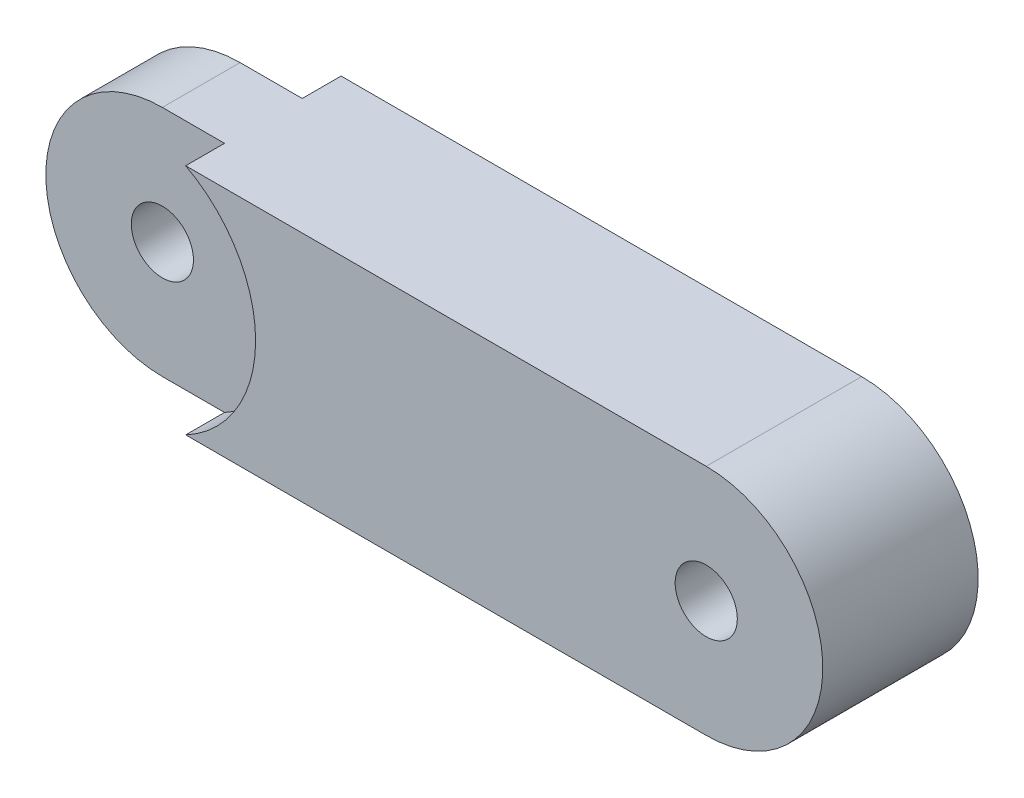
SolidWorks part; units mm, degrees
ref_plane "前视基准面" through (0, 0, 0) normal (0, 0, 1) x (1, 0, 0)
ref_plane "上视基准面" through (0, 0, 0) normal (0, 1, 0) x (1, 0, 0)
ref_plane "右视基准面" through (0, 0, 0) normal (1, 0, 0) x (0, 0, -1)
other "Configuration Table"
sketch "草图1" plane through (0, 0, 0) normal (0, 0, 1) x (1, 0, 0)
  line L0 (0, 15) -> (75, 15)
  line L1 (0, -15) -> (75, -15)
  arc A0 (0, 15) -> (0, -15) centre (0, 0) ccw
  arc A1 (75, -15) -> (75, 15) centre (75, 0) ccw
  circle A2 centre (0, 0) radius 4
  circle A3 centre (75, 0) radius 4
extrude "凸台-拉伸1" add sketch "草图1" along normal blind 20
sketch "草图2" plane through (0, 0, 0) normal (0, 0, 1) x (1, 0, 0)
  circle A0 centre (0, 0) radius 17
extrude "切除-拉伸1" cut sketch "草图2" along normal blind 5
extrude "切除-拉伸2" cut sketch "草图2<2>" along normal blind 5 from offset 15
sketch "草图2<2>" plane through (0, 0, 0) normal (0, 0, 1) x (1, 0, 0) same geometry as "草图2"
